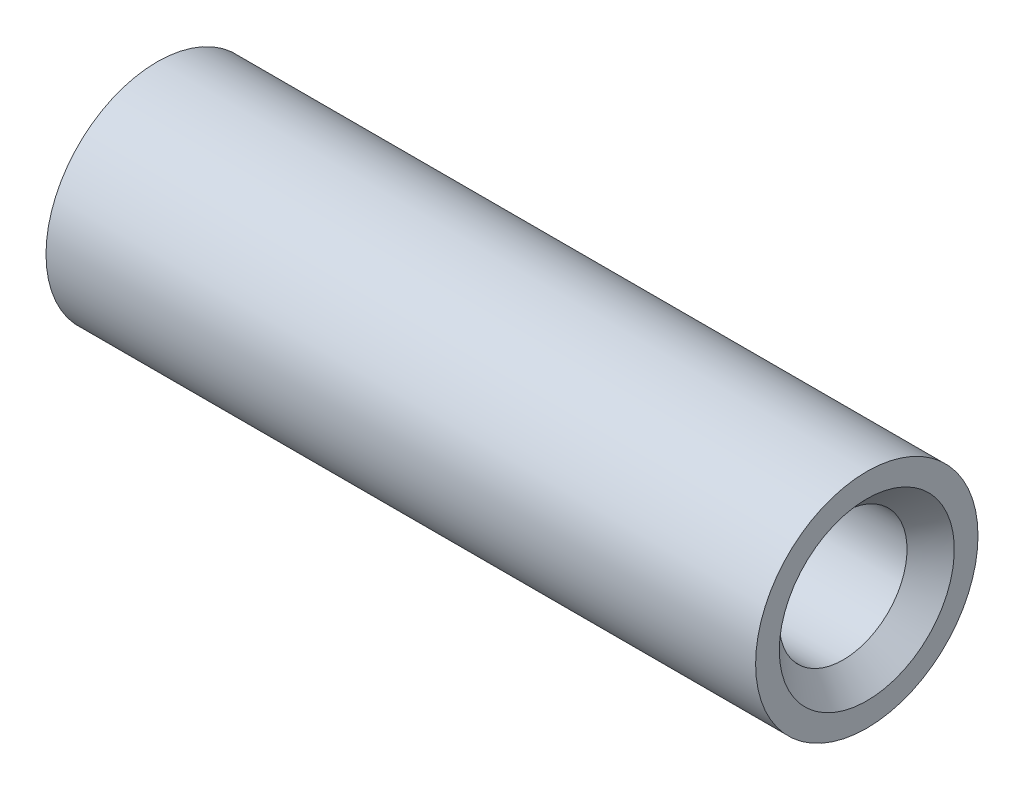
SolidWorks part; units mm, degrees
ref_plane "Front" through (0, 0, 0) normal (0, 0, 1) x (1, 0, 0)
ref_plane "Top" through (0, 0, 0) normal (0, 1, 0) x (1, 0, 0)
ref_plane "Right" through (0, 0, 0) normal (1, 0, 0) x (0, 0, -1)
sketch "Sketch1" plane through (0, 0, 0) normal (0, 0, 1) x (1, 0, 0)
  line L0 (0, 0) -> (25.4984, 0) construction
  line L1 (-2.5, 0) -> (-2.5, 4.05)
  line L2 (-2.5, 4.05) -> (-22.5, 4.05)
  line L3 (-22.5, 4.05) -> (-22.5, 7.0514)
  line L4 (-22.5, 7.0514) -> (22.5, 7.0514)
  line L5 (22.5, 7.0514) -> (22.5, 4.05)
  line L6 (22.5, 4.05) -> (2.5, 4.05)
  line L7 (2.5, 4.05) -> (2.5, 0)
  line L8 (2.5, 0) -> (-2.5, 0)
  line L9 (0, 0) -> (0, 11.8157) construction
  dimension "D1" = 8.1
  dimension "D2" = 8.1
  dimension "D3" = 20
  dimension "D4" = 5
  dimension "D5" = 3.0014
revolve "Revolve1" add sketch "Sketch1" angle 360 about L0
chamfer "Chamfer1" distance 1.5 angle 45 2 edges at (-22.5, 0, 4.05) (22.5, 0, 4.05)
